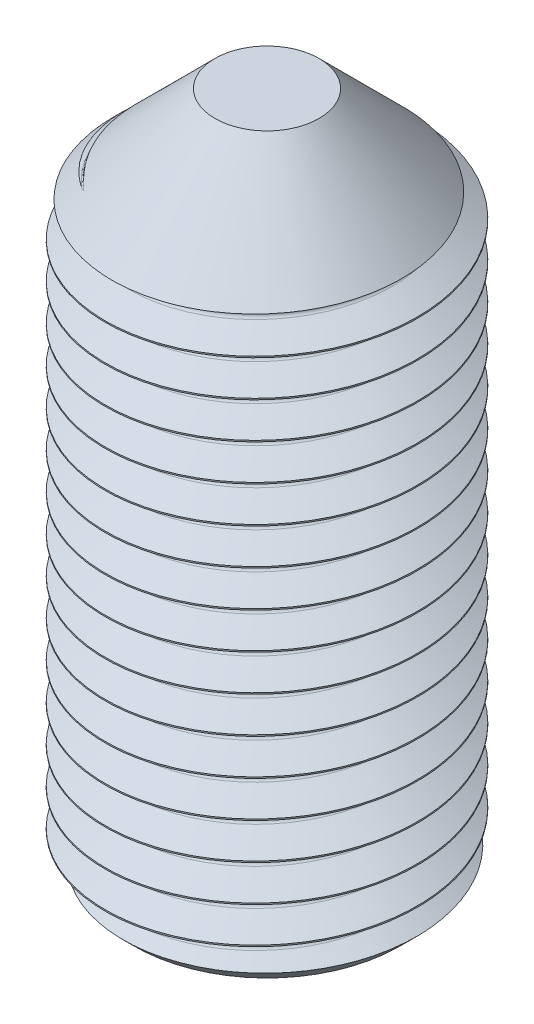
SolidWorks part; units mm, degrees
ref_plane "Front Plane" through (0, 0, 0) normal (0, 0, 1) x (1, 0, 0)
ref_plane "Top Plane" through (0, 0, 0) normal (0, 1, 0) x (1, 0, 0)
ref_plane "Right Plane" through (0, 0, 0) normal (1, 0, 0) x (0, 0, -1)
sketch "Sketch1" plane through (0, 0, 0) normal (0, 1, 0) x (1, 0, 0)
  circle A0 centre (0, 0) radius 15
  dimension "D1" = 30
extrude "Boss-Extrude1" add sketch "Sketch1" along normal mid plane 65
sketch "Sketch2" plane through (0, 0, 0) normal (0, 0, 1) x (1, 0, 0)
  line L0 (5, 32.5) -> (29.3582, 8.1418)
  line L1 (29.3582, 8.1418) -> (29.3582, -15.8918)
  line L2 (29.3582, -15.8918) -> (12.75, -32.5)
  line L3 (12.75, -32.5) -> (12.75, -71.5349)
  line L4 (12.75, -71.5349) -> (75.1124, -71.5349)
  line L5 (75.1124, -71.5349) -> (75.1124, 77.7752)
  line L6 (75.1124, 77.7752) -> (5, 77.7752)
  line L7 (5, 77.7752) -> (5, 32.5)
  line L8 (0, 0) -> (0, -3.1523) construction
  line L9 (15, 32.5) -> (-15, 32.5) construction
  line L10 (-15, -32.5) -> (15, -32.5) construction
  dimension "D1" = 10
  dimension "D2" = 25.5
  dimension "D3" = 135
  dimension "D4" = 135
revolve "Cut-Revolve1" cut sketch "Sketch2" angle 360 about L8
sketch "Sketch3" plane through (0, -32.5, 0) normal (0, -1, 0) x (1, 0, 0)
  line L1 (7.1, -4.0992) -> (7.1, 4.0992)
  line L2 (7.1, 4.0992) -> (0, 8.1984)
  line L3 (0, 8.1984) -> (-7.1, 4.0992)
  line L4 (-7.1, 4.0992) -> (-7.1, -4.0992)
  line L5 (-7.1, -4.0992) -> (0, -8.1984)
  line L6 (0, -8.1984) -> (7.1, -4.0992)
  circle A0 centre (0, 0) radius 7.1 construction
  dimension "D1" = 14.2
extrude "Cut-Extrude1" cut sketch "Sketch3" against normal blind 16
sketch "Sketch4" plane through (0, -32.5, 0) normal (0, -1, 0) x (1, 0, 0)
  circle A0 centre (0, 0) radius 15 construction
  circle A1 centre (0, 0) radius 15
curve "Helix/Spiral1" pitch 3.5 height 73.5 turns 21
sketch "Sketch5" plane through (0, 0, 0) normal (0, 0, 1) x (1, 0, 0)
  line L1 (15.1021, -31.2925) -> (12.6208, -32.7251)
  line L2 (12.6208, -33.3499) -> (15.1021, -34.7825)
  line L3 (15.1021, -34.7825) -> (15.1021, -31.2925)
  circle A0 centre (14.0946, -33.0375) radius 1.0075 construction
  arc A1 (12.6208, -32.7251) -> (12.6208, -33.3499) centre (12.8012, -33.0375) ccw
  point P7 (14.3612, -35.5299)
  point P8 (13.9548, -35.4495)
  point P9 (14.0022, -35.459)
  point P10 (11.1317, -28.059)
  point P11 (11.1898, -28.0572)
  point P12 (14.5674, -32.7167)
  point P13 (14.3411, -32.1921)
  point P14 (14.0946, -33.0375)
  dimension "D2" = 0.3608
  dimension "D1" = 3.49
sweep "Cut-Sweep1" cut profiles "Sketch5" path "Helix/Spiral1"
sketch "Sketch6" plane through (0, -32.5, 0) normal (0, -1, 0) x (1, 0, 0)
  circle A0 centre (0, 0) radius 8.1984
extrude "Cut-Extrude2" cut sketch "Sketch6" against normal blind 1.5 draft 75
